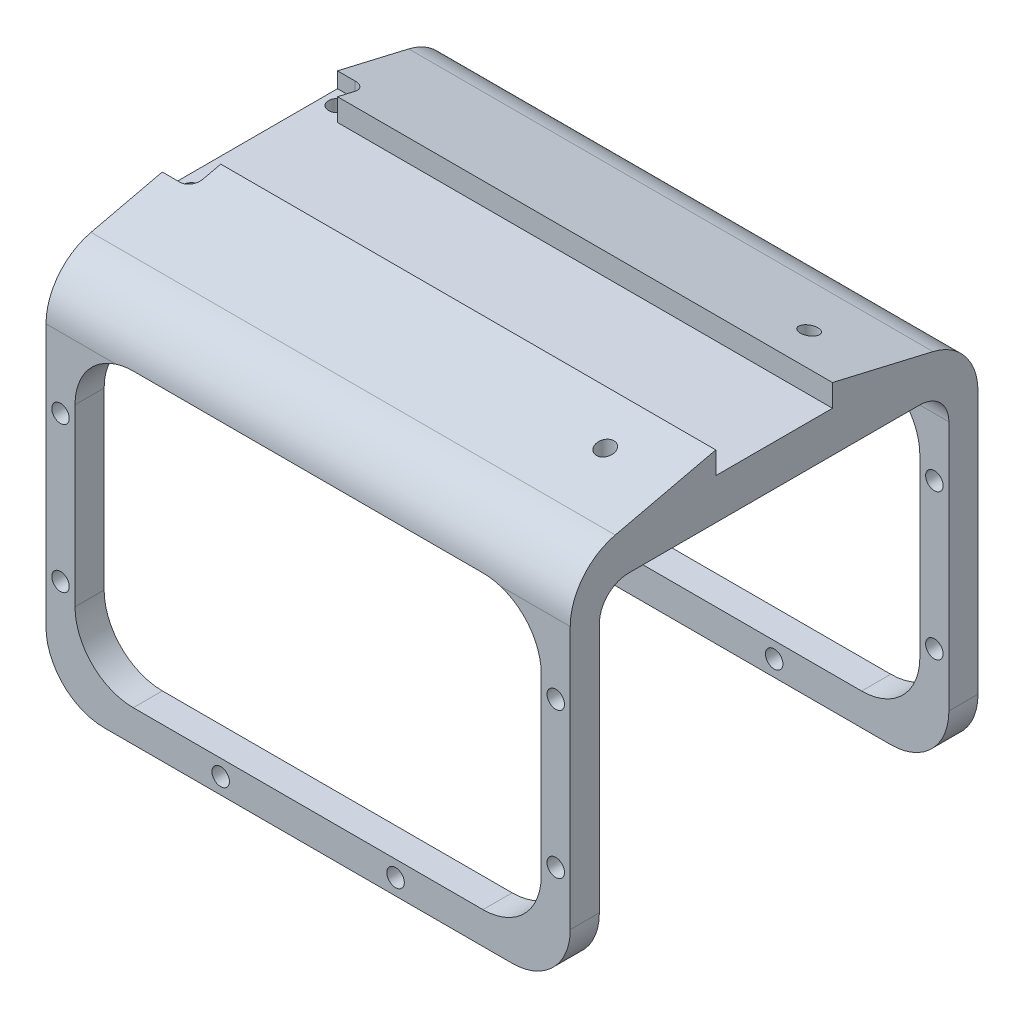
SolidWorks part; units mm, degrees
other "Markup1"
sketch "Sketch21" plane through (45, 39.5, 70) normal (0.1875, 0.7157, 0.6727) x (0.9821, -0.1502, -0.1139)
ref_plane "Front Plane" through (0, 0, 0) normal (0, 0, 1) x (1, 0, 0)
ref_plane "Top Plane" through (0, 0, 0) normal (0, 1, 0) x (1, 0, 0)
ref_plane "Right Plane" through (0, 0, 0) normal (1, 0, 0) x (0, 0, -1)
sketch "Sketch1" plane through (0, 0, 0) normal (0, 0, 1) x (1, 0, 0)
  line L1 (-45, 27.5) -> (45, 27.5)
  line L2 (-45, 27.5) -> (-45, -27.5)
  line L3 (-45, -27.5) -> (45, -27.5)
  line L4 (45, 27.5) -> (45, -27.5)
  line L5 (-45, 27.5) -> (45, -27.5) construction
  line L6 (-45, -27.5) -> (45, 27.5) construction
  point P0 (0, 0)
  dimension "D1" = 90
  dimension "D2" = 55
extrude "Boss-Extrude1" add sketch "Sketch1" along normal blind 70
sketch "Sketch2" plane through (-45, 0, 0) normal (-1, 0, 0) x (0, 0, 1)
  line L0 (70, -27.5) -> (0, -27.5) construction
  line L1 (5, 22.5) -> (65, 22.5)
  line L2 (5, 22.5) -> (5, -27.5)
  line L3 (5, -27.5) -> (65, -27.5)
  line L4 (65, 22.5) -> (65, -27.5)
  line L5 (0, 27.5) -> (0, -27.5) construction
  line L6 (70, 27.5) -> (0, 27.5) construction
  line L7 (70, 27.5) -> (70, -27.5) construction
  dimension "D1" = 5
  dimension "D2" = 5
  dimension "D3" = 5
extrude "Cut-Extrude1" cut sketch "Sketch2" against normal blind 117
sketch "Sketch3" plane through (0, 0, 70) normal (0, 0, 1) x (1, 0, 0)
  line L0 (0, 27.5) -> (0, -27.5) construction
  line L1 (45, 27.5) -> (-45, 27.5) construction
  line L2 (-45, -27.5) -> (45, -27.5) construction
  line L4 (-40, 25) -> (40, 25)
  line L5 (-40, 25) -> (-40, -25)
  line L6 (-40, -25) -> (40, -25)
  line L7 (40, 25) -> (40, -25)
  line L8 (-40, 25) -> (40, -25) construction
  line L9 (-40, -25) -> (40, 25) construction
  point P6 (0, 0)
  dimension "D1" = 80
  dimension "D2" = 50
sketch "Sketch4" plane through (0, 27.5, 0) normal (0, 1, 0) x (1, 0, 0)
  line L1 (-45, 0) -> (45, 0)
  line L2 (-45, 0) -> (-45, -70)
  line L3 (-45, -70) -> (45, -70)
  line L4 (45, 0) -> (45, -70)
extrude "Boss-Extrude2" add sketch "Sketch4" along normal blind 5
sketch "Sketch5" plane through (45, 0, 0) normal (1, 0, 0) x (0, 0, -1)
  line L0 (-5, 22.5) -> (-5, 30.1801) construction
  line L2 (-65, 22.5) -> (-5, 22.5)
  line L3 (-65, 22.5) -> (-65, 27.5)
  line L4 (-65, 27.5) -> (-5, 27.5)
  line L5 (-5, 22.5) -> (-5, 27.5)
  dimension "D1" = 5
extrude "Cut-Extrude2" cut sketch "Sketch5" against normal blind 144
sketch "Sketch6" plane through (0, 0, 70) normal (0, 0, 1) x (1, 0, 0)
  line L0 (-40, 25.02) -> (40.02, 25.02)
  line L5 (-40, 25) -> (40, -25) construction
  line L6 (-40, -25) -> (40, 25) construction
  line L7 (40.02, 25.02) -> (40.02, -25.02)
  line L8 (40.02, -25.02) -> (-40.02, -25.02)
  line L9 (-40.02, -25.02) -> (-40.02, 25.02)
  line L10 (-40.02, 25.02) -> (-37.6472, 25.02)
  line L11 (45, -27.5) -> (45, 32.5) construction
  point P0 (0, 0)
  dimension "D1" = 4.98
extrude "Cut-Extrude4" cut sketch "Sketch6" against normal blind 144 contours L10 L9 L8 L7 L0
sketch "Sketch7" plane through (0, -27.5, 0) normal (0, -1, 0) x (1, 0, 0)
  line L1 (-45, 70) -> (45, 70)
  line L2 (-45, 70) -> (-45, 65)
  line L3 (-45, 65) -> (45, 65)
  line L4 (45, 70) -> (45, 65)
  line L5 (-45, 5) -> (45, 5)
  line L6 (-45, 5) -> (-45, 0)
  line L7 (-45, 0) -> (45, 0)
  line L8 (45, 5) -> (45, 0)
extrude "Boss-Extrude3" add sketch "Sketch7" along normal blind 3 contours L2 L1 L4 L3 | L6 L5 L8 L7
sketch "Sketch8" plane through (0, 0, 0) normal (0, 0, -1) x (-1, 0, 0)
  line L0 (-40.02, 0) -> (40.02, 0) construction
  line L1 (-40.02, 25.02) -> (-40.02, -25.02) construction
  line L2 (40.02, -25.02) -> (40.02, 25.02) construction
  line L3 (-40.02, 25) -> (40.02, 25) construction
  line L4 (-40.02, -25) -> (40.02, -25) construction
  line L5 (40.02, 0) -> (40.02, -25) construction
  line L6 (40.02, 25) -> (40.02, 0) construction
  line L7 (40.02, 12.5) -> (-40.02, 12.5) construction
  line L8 (40.02, -12.5) -> (-40.02, -12.5) construction
  line L9 (40.02, 12.5) -> (45, 12.5) construction
  line L10 (45, 32.5) -> (45, -30.5) construction
  line L11 (40.02, -12.5) -> (45, -12.5) construction
  line L12 (-40.02, -12.5) -> (-45, -12.5) construction
  line L13 (-45, -30.5) -> (-45, 32.5) construction
  line L14 (-40.02, 12.5) -> (-45, 12.5) construction
  circle A0 centre (-42.51, 12.5) radius 1.5
  circle A1 centre (-42.51, -12.5) radius 1.5
  circle A2 centre (42.51, -12.5) radius 1.5
  circle A3 centre (42.51, 12.5) radius 1.5
  dimension "D3" = 3
  dimension "D4" = 3
  dimension "D5" = 3
  dimension "D6" = 3
  dimension "D1" = 25
  dimension "D2" = 25
extrude "Cut-Extrude5" cut sketch "Sketch8" against normal blind 155
fillet "Fillet1" radius 10 8 edges at (40.02, -25.02, 2.5) (-40.02, -25.02, 2.5) (-40.02, 25.02, 2.5) (40.02, 25.02, 2.5) (40.02, -25.02, 67.5) (-40.02, -25.02, 67.5) (-40.02, 25.02, 67.5) (40.02, 25.02, 67.5)
fillet "Fillet2" radius 10 4 edges at (45, -30.5, 67.5) (45, -30.5, 2.5) (-45, -30.5, 67.5) (-45, -30.5, 2.5)
sketch "Sketch9" plane through (0, 32.5, 0) normal (0, 1, 0) x (1, 0, 0)
  line L0 (-45, -35) -> (35, -35) construction
  line L1 (-45, 0) -> (-45, -70) construction
  line L2 (35, -70) -> (35, 0) construction
  line L4 (-45, -30) -> (35, -30)
  line L5 (-45, -30) -> (-45, -40)
  line L6 (-45, -40) -> (35, -40)
  line L7 (35, -30) -> (35, -40)
  line L8 (-45, -30) -> (35, -40) construction
  line L9 (-45, -40) -> (35, -30) construction
  point P6 (-5, -35)
  dimension "D1" = 10
extrude "Boss-Extrude4" add sketch "Sketch9" along normal blind 7
sketch "Sketch10" plane through (-45, 0, 0) normal (-1, 0, 0) x (0, 0, 1)
  line L0 (40, 39.5) -> (70, 32.5)
  line L1 (30, 39.5) -> (0, 32.5)
  line L2 (0, 32.5) -> (30, 32.5)
  line L3 (30, 32.5) -> (30, 39.5)
  line L4 (40, 39.5) -> (40, 32.5)
  line L5 (40, 32.5) -> (70, 32.5)
extrude "Boss-Extrude5" add sketch "Sketch10" against normal blind 80 contours L3 L1 L2 | L5 L0 L4
sketch "Sketch11" plane through (35, 0, 0) normal (1, 0, 0) x (0, 0, -1)
  line L0 (-70, 32.5) -> (-40, 39.5)
  line L1 (-40, 39.5) -> (-30, 39.5)
  line L2 (-30, 39.5) -> (0, 32.5)
  line L3 (0, 32.5) -> (-70, 32.5)
extrude "Boss-Extrude6" add sketch "Sketch11" along normal blind 10
fillet "Fillet3" radius 10 2 edges at (0, 32.5, 70) (0, 32.5, 0)
fillet "Fillet4" radius 5 2 edges at (0, 27.5, 65) (0, 27.5, 5)
sketch "Sketch12" plane through (0, 39.5, 0) normal (0, 1, 0) x (1, 0, 0)
  line L0 (-45, -35) -> (45, -35) construction
  line L1 (-45, -30) -> (-45, -40) construction
  line L2 (45, -30) -> (45, -40) construction
  line L4 (-45, -33.5) -> (45, -33.5)
  line L5 (-45, -33.5) -> (-45, -36.5)
  line L6 (-45, -36.5) -> (45, -36.5)
  line L7 (45, -33.5) -> (45, -36.5)
  line L8 (-45, -33.5) -> (45, -36.5) construction
  line L9 (-45, -36.5) -> (45, -33.5) construction
  point P6 (0, -35)
  dimension "D1" = 3
extrude "Cut-Extrude6" cut sketch "Sketch12" against normal blind 10
sketch "Sketch13" plane through (0, 29.5, 0) normal (0, 1, 0) x (1, 0, 0)
  line L1 (-45, -33.5) -> (45, -33.5)
  line L2 (-45, -33.5) -> (-45, -36.5)
  line L3 (-45, -36.5) -> (45, -36.5)
  line L4 (45, -33.5) -> (45, -36.5)
extrude "Boss-Extrude7" add sketch "Sketch13" along normal blind 10
sketch "Sketch14" plane through (0, 0, 70) normal (0, 0, 1) x (1, 0, 0)
  line L0 (-30.02, -25.02) -> (30.02, -25.02) construction
  line L1 (30.02, -25.02) -> (0, -25.02) construction
  line L2 (0, -25.02) -> (0, -30.5) construction
  line L3 (-35, -30.5) -> (35, -30.5) construction
  line L4 (0, -30.5) -> (15.01, -25.02) construction
  line L5 (15.01, -25.02) -> (15.01, -30.5) construction
  line L6 (15.01, -30.5) -> (0, -25.02) construction
  line L7 (0, -25.02) -> (-30.02, -25.02) construction
  line L8 (-30.02, -25.02) -> (-15.01, -25.02) construction
  line L9 (-15.01, -25.02) -> (-15.01, -30.5) construction
  line L10 (-15.01, -30.5) -> (0, -25.02) construction
  line L11 (0, -25.02) -> (-15.01, -25.02) construction
  line L12 (-15.01, -25.02) -> (0, -30.5) construction
  circle A0 centre (-15.01, -27.76) radius 1.5
  circle A1 centre (15.01, -27.76) radius 1.5
  dimension "D1" = 3
  dimension "D2" = 3
extrude "Cut-Extrude7" cut sketch "Sketch14" against normal blind 90
sketch "Sketch15" plane through (45, 0, 0) normal (1, 0, 0) x (0, 0, -1)
  line L0 (-35, 39.5) -> (-35, 27.5) construction
  line L1 (-30, 39.5) -> (-40, 39.5) construction
  line L2 (-10, 27.5) -> (-60, 27.5) construction
  line L4 (-50, 25.5) -> (-20, 25.5)
  line L5 (-50, 25.5) -> (-50, 29.5)
  line L6 (-50, 29.5) -> (-20, 29.5)
  line L7 (-20, 25.5) -> (-20, 29.5)
  line L8 (-50, 25.5) -> (-20, 29.5) construction
  line L9 (-50, 29.5) -> (-20, 25.5) construction
  dimension "D1" = 30
  dimension "D2" = 4
extrude "Cut-Extrude8" cut sketch "Sketch15" against normal blind 28
sketch "Sketch16" plane through (0, 29.5, 0) normal (0, -1, 0) x (1, 0, 0)
  line L0 (31, 50) -> (31, 20) construction
  line L1 (17, 50) -> (45, 50) construction
  line L2 (17, 20) -> (45, 20) construction
  line L3 (31, 20) -> (17, 35) construction
  line L4 (17, 20) -> (17, 50) construction
  line L5 (17, 35) -> (45, 35) construction
  line L6 (45, 20) -> (45, 50) construction
  line L7 (31, 50) -> (31, 55) construction
  line L8 (31, 55) -> (31, 20) construction
  line L9 (31, 20) -> (31, 15) construction
  line L12 (28.5, 55) -> (33.5, 55)
  line L13 (28.5, 55) -> (28.5, 50)
  line L14 (28.5, 50) -> (33.5, 50)
  line L15 (33.5, 55) -> (33.5, 50)
  line L16 (28.5, 55) -> (33.5, 50) construction
  line L17 (28.5, 50) -> (33.5, 55) construction
  line L18 (28.5, 20) -> (33.5, 20)
  line L19 (28.5, 20) -> (28.5, 15)
  line L20 (28.5, 15) -> (33.5, 15)
  line L21 (33.5, 20) -> (33.5, 15)
  line L22 (28.5, 20) -> (33.5, 15) construction
  line L23 (28.5, 15) -> (33.5, 20) construction
  circle A1 centre (31, 42.01) radius 2.5
  circle A2 centre (38.01, 35) radius 2.5
  circle A3 centre (23.99, 35) radius 2.5
  circle A4 centre (31, 27.99) radius 2.5
  circle A5 centre (31, 35) radius 2.5
  circle A6 centre (31, 52.5) radius 1.5
  circle A7 centre (31, 17.5) radius 1.5
  arc A8 (28.5401, 28.4358) -> (33.4599, 28.4358) centre (31, 35) ccw
  point P13 (31, 17.5)
  point P27 (31, 52.5)
  dimension "D1" = 5
  dimension "D2" = 5
  dimension "D3" = 5
  dimension "D4" = 5
  dimension "D5" = 5
  dimension "D6" = 5
  dimension "D10" = 3
  dimension "D11" = 3
  dimension "D7" = 5
  dimension "D8" = 5
  dimension "D9" = 5
sketch "Sketch18" plane through (0, 39.5, 0) normal (0, 1, 0) x (1, 0, 0)
  line L0 (-45, -35) -> (45, -35) construction
  line L1 (-45, -30) -> (-45, -40) construction
  line L2 (45, -40) -> (45, -62.2723) construction
  line L3 (-45, -24.98) -> (45, -24.98)
  line L4 (-45, -24.98) -> (-45, -45.02)
  line L5 (-45, -45.02) -> (45, -45.02)
  line L6 (45, -24.98) -> (45, -45.02)
  line L7 (-45, -24.98) -> (45, -45.02) construction
  line L8 (-45, -45.02) -> (45, -24.98) construction
  line L9 (-45, -24.98) -> (-40, -24.98) construction
  line L10 (-45, -24.98) -> (-39.98, -24.98)
  line L11 (-45, -24.98) -> (-45, -19.96)
  line L12 (-45, -19.96) -> (-39.98, -19.96)
  line L13 (-39.98, -24.98) -> (-39.98, -19.96)
  line L14 (-45, -45.02) -> (-39.98, -45.02)
  line L15 (-45, -45.02) -> (-45, -50.04)
  line L16 (-45, -50.04) -> (-39.98, -50.04)
  line L17 (-39.98, -45.02) -> (-39.98, -50.04)
  line L18 (-40, -24.98) -> (-45, -19.98) construction
  line L19 (-45, -45.02) -> (-40, -45.02) construction
  line L20 (-40, -45.02) -> (-45, -50.02) construction
  circle A1 centre (-42.5, -47.52) radius 1.5
  circle A2 centre (-42.5, -22.48) radius 1.5
  point P5 (0, -35)
  dimension "D7" = 0.02
  dimension "D10" = 3
  dimension "D11" = 3
  dimension "D1" = 20.04
  dimension "D2" = 5.02
  dimension "D3" = 5.02
  dimension "D4" = 5.02
  dimension "D5" = 5.02
  dimension "D6" = 5
  dimension "D8" = 5
  dimension "D9" = 5
sketch "Sketch19" plane through (0, 39.5, 0) normal (0, 1, 0) x (1, 0, 0)
  line L1 (-45, -24.98) -> (45, -24.98)
  line L2 (-45, -24.98) -> (-45, -45.02)
  line L3 (-45, -45.02) -> (45, -45.02)
  line L4 (45, -24.98) -> (45, -45.02)
  line L5 (-45, -19.96) -> (-39.98, -19.96)
  line L6 (-45, -19.96) -> (-45, -24.98)
  line L7 (-45, -24.98) -> (-39.98, -24.98)
  line L8 (-39.98, -19.96) -> (-39.98, -24.98)
  line L9 (-45, -45.02) -> (-39.98, -45.02)
  line L10 (-45, -45.02) -> (-45, -50.04)
  line L11 (-45, -50.04) -> (-39.98, -50.04)
  line L12 (-39.98, -45.02) -> (-39.98, -50.04)
  line M1 (-45, -30) -> (-45, -40)
  line M2 (-45, -40) -> (45, -40)
  line M3 (45, -40) -> (45, -30)
  line M4 (45, -30) -> (-45, -30)
extrude "Cut-Extrude12" cut sketch "Sketch19" against normal blind 5 contours M4 M1 M2 M3 | L8 L5 L6 L1 | L4 L1 L2 M4 | L4 L2 L3 M2 | L12 L3 L10 L11
sketch "Sketch20" plane through (0, 34.5, 0) normal (0, 1, 0) x (1, 0, 0)
  circle A0 centre (-42.5, -22.48) radius 1.5
  circle A1 centre (-42.5, -47.52) radius 1.5
extrude "Cut-Extrude13" cut sketch "Sketch20" against normal blind 18
fillet "Fillet5" radius 2 2 edges at (-39.98, 35.8287, 50.04) (-39.98, 35.8287, 19.96)
sketch "Sketch22" plane through (0, 27.5, 0) normal (0, -1, 0) x (1, 0, 0)
  line L1 (17, 50) -> (45, 50)
  line L2 (17, 50) -> (17, 20)
  line L3 (17, 20) -> (45, 20)
  line L4 (45, 50) -> (45, 20)
extrude "Boss-Extrude9" add sketch "Sketch22" against normal blind 4
sketch "Sketch24" plane through (0, 27.5, 0) normal (0, -1, 0) x (1, 0, 0)
  line L0 (45, 35) -> (22, 35) construction
  line L1 (45, 10) -> (45, 60) construction
  line L3 (22, 60.6815) -> (22, 9.3185) construction
  line L4 (30.02, 60.6815) -> (-30.02, 60.6815) construction
  line L5 (-30.02, 9.3185) -> (30.02, 9.3185) construction
  line L6 (22, 35) -> (45, 35) construction
  line L7 (33.5, 57.3009) -> (33.5, 12.5338) construction
  line L8 (22, 50) -> (45, 50)
  line L9 (22, 50) -> (22, 20)
  line L10 (22, 20) -> (45, 20)
  line L11 (45, 50) -> (45, 20)
  line L12 (22, 50) -> (45, 20) construction
  line L13 (22, 20) -> (45, 50) construction
  line L15 (31, 55) -> (36, 55)
  line L16 (31, 55) -> (31, 50)
  line L17 (31, 50) -> (36, 50)
  line L18 (36, 55) -> (36, 50)
  line L19 (31, 55) -> (36, 50) construction
  line L20 (31, 50) -> (36, 55) construction
  line L21 (31, 15) -> (36, 15)
  line L22 (31, 15) -> (31, 20)
  line L23 (31, 20) -> (36, 20)
  line L24 (36, 15) -> (36, 20)
  line L25 (31, 15) -> (36, 20) construction
  line L26 (31, 20) -> (36, 15) construction
  circle A0 centre (33.5, 52.5) radius 1.5
  circle A1 centre (33.5, 17.5) radius 1.5
  point P1 (33.5, 35)
  point P17 (33.5, 52.5)
  point P22 (33.5, 17.5)
  dimension "D7" = 3
  dimension "D8" = 3
  dimension "D1" = 23
  dimension "D2" = 30
  dimension "D3" = 5
  dimension "D4" = 5
  dimension "D5" = 5
  dimension "D6" = 5
extrude "Cut-Extrude14" cut sketch "Sketch24" against normal blind 26 contours A0 | A1
sketch "Sketch25" plane through (0, 27.5, 0) normal (0, -1, 0) x (1, 0, 0)
  line L0 (-42.5, 47.52) -> (-42.5, 22.48) construction
  line L2 (-39.5, 50.52) -> (-45.5, 50.52)
  line L3 (-39.5, 50.52) -> (-39.5, 44.52)
  line L4 (-39.5, 44.52) -> (-45.5, 44.52)
  line L5 (-45.5, 50.52) -> (-45.5, 44.52)
  line L6 (-39.5, 50.52) -> (-45.5, 44.52) construction
  line L7 (-39.5, 44.52) -> (-45.5, 50.52) construction
  line L8 (-39.5, 25.48) -> (-45.5, 25.48)
  line L9 (-39.5, 25.48) -> (-39.5, 19.48)
  line L10 (-39.5, 19.48) -> (-45.5, 19.48)
  line L11 (-45.5, 25.48) -> (-45.5, 19.48)
  line L12 (-39.5, 25.48) -> (-45.5, 19.48) construction
  line L13 (-39.5, 19.48) -> (-45.5, 25.48) construction
  circle A0 centre (-42.5, 47.52) radius 1.5
  circle A1 centre (-42.5, 22.48) radius 1.5
  dimension "D1" = 25.04
  dimension "D2" = 6
  dimension "D3" = 6
  dimension "D4" = 6
  dimension "D5" = 6
extrude "Boss-Extrude11" add sketch "Sketch25" against normal blind 5
